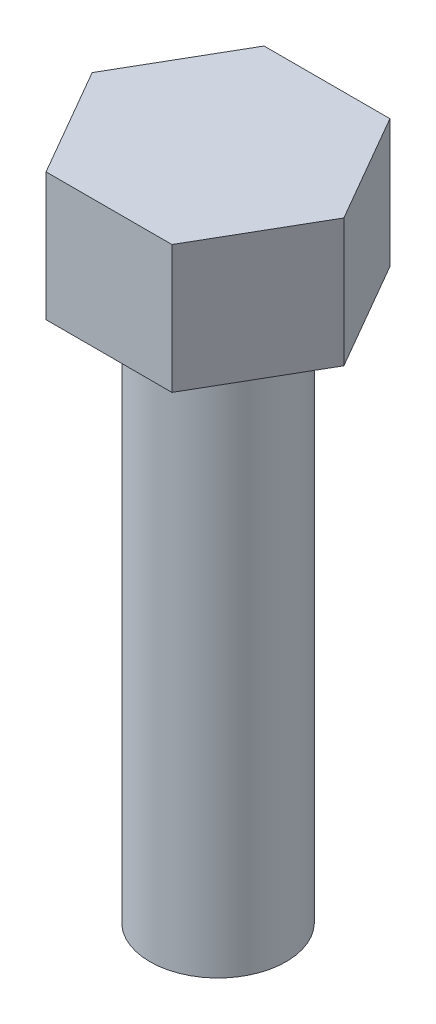
SolidWorks part; units mm, degrees
ref_plane "Front (1)" through (0, 0, 0) normal (0, 0, 1) x (1, 0, 0)
ref_plane "Top (2)" through (0, 0, 0) normal (0, 1, 0) x (1, 0, 0)
ref_plane "Right (3)" through (0, 0, 0) normal (1, 0, 0) x (0, 0, -1)
ref_axis "X Axis" through (13.5064, 0, 0) along (-1, 0, 0)
ref_axis "Y Axis" through (0, 12.3593, 0) along (0, -1, 0)
ref_axis "Z Axis" through (0, 0, 14.1119) along (0, 0, -1)
sketch "skHead" plane through (0, 0, 0) normal (0, 1, 0) x (1, 0, 0)
  line L1 (4.6188, 0) -> (2.3094, 4)
  line L2 (2.3094, 4) -> (-2.3094, 4)
  line L3 (-2.3094, 4) -> (-4.6188, 0)
  line L4 (-4.6188, 0) -> (-2.3094, -4)
  line L5 (-2.3094, -4) -> (2.3094, -4)
  line L6 (2.3094, -4) -> (4.6188, 0)
  circle A0 centre (0, 0) radius 4 construction
  dimension "Width" = 8
extrude "Head" add sketch "skHead" along normal blind 4.7
sketch "skBody" plane through (0, 0, 0) normal (0, 1, 0) x (1, 0, 0)
  circle A0 centre (0, 0) radius 2.5
  dimension "Size" = 5
extrude "Body" add sketch "skBody" against normal blind 20
